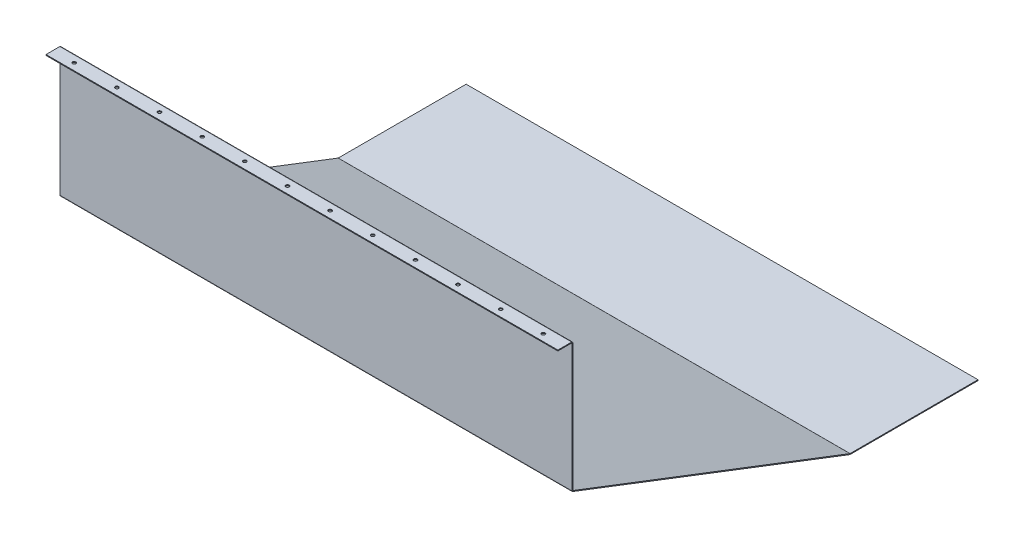
SolidWorks part; units mm, degrees
note: The reader was unsure of these and kept them because the rebuilt part matched: thickness of "Base-Flange1", "Edge-Flange1", "Sheet-Metal3", "Sheet-Metal4", "Sheet-Metal5"; bend radius of "BaseBend1", "BaseBend2"; flange length of "Edge-Flange1".
material "AISI 304"
ref_plane "Front Plane" through (0, 0, 0) normal (0, 0, 1) x (1, 0, 0)
ref_plane "Top Plane" through (0, 0, 0) normal (0, 1, 0) x (1, 0, 0)
ref_plane "Right Plane" through (0, 0, 0) normal (1, 0, 0) x (0, 0, -1)
sketch "Sketch1" plane through (0, 0, 0) normal (1, 0, 0) x (0, 0, -1)
  line L0 (0, 0) -> (0, -300)
  line L1 (0, -300) -> (650, -550)
  line L3 (950, 0) -> (0, 0) construction
  line L4 (0, -300) -> (950, -300) construction
  line L5 (950, 0) -> (950, -550) construction
  line L6 (950, -550) -> (650, -550)
  dimension "D3" = 950
  dimension "D2" = 550
  dimension "D4" = 300
  dimension "D1" = 300
base flange "Base-Flange1" sketch "Sketch1" end condition mid plane depth 1200 reverse direction no thickness 2 reverse thickness direction yes bend radius 0.7366
bend "BaseBend1" bend radius 0.7366 bend angle 21.038 parameters "D5"=1
bend "BaseBend2" bend radius 0.7366 bend angle 68.962 parameters "D5"=2
edge flange "Edge-Flange1" sketch "Sketch6" flange angle 90 flange length 35 flange position bend outside bend radius 0.7366 thickness 2 relief rectangular parameters "D6"=10
sketch "Sketch6" plane through (0, 0, 2) normal (0, -1, 0) x (1, 0, 0)
  line L2 (-600, 0) -> (-600, 33)
  line L3 (-600, 33) -> (600, 33)
  line L4 (600, 33) -> (600, 0)
  line L5 (600, 0) -> (-600, 0) construction
  line L6 (600, 0) -> (-600, 0)
bend "EdgeBend1" bend radius 0.7366 bend angle 90 parameters "D5"=3
sketch "Sketch7" plane through (0, 0.7366, 0) normal (0, -1, 0) x (1, 0, 0)
  line L0 (-600, 18.8683) -> (-550, 18.8683) construction
  line L2 (550, 18.8683) -> (600, 18.8683) construction
  line L5 (-600, 35) -> (-600, 2.7366) construction
  line L6 (600, 2.7366) -> (600, 35) construction
  circle A0 centre (-550, 18.8683) radius 4
  circle A1 centre (-450, 18.8683) radius 4
  circle A2 centre (-350, 18.8683) radius 4
  circle A3 centre (-250, 18.8683) radius 4
  circle A4 centre (-150, 18.8683) radius 4
  circle A5 centre (-50, 18.8683) radius 4
  circle A6 centre (50, 18.8683) radius 4
  circle A7 centre (150, 18.8683) radius 4
  circle A8 centre (250, 18.8683) radius 4
  circle A9 centre (350, 18.8683) radius 4
  circle A10 centre (450, 18.8683) radius 4
  circle A11 centre (550, 18.8683) radius 4
  dimension "D1" = 8
  dimension "D3" = 100
  dimension "D2" = 12
extrude "Cut-Extrude1" cut sketch "Sketch7" against normal blind 10
sketch "Bend-Lines1" [suppressed] plane through (0, 0, 0) normal (0, 1, 0) x (1, 0, 0)
sketch "Bounding-Box1" [suppressed] plane through (0, 0, 0) normal (0, 1, 0) x (1, 0, 0)
sheet metal parameters "Sheet-Metal3" thickness 2 parameters "D1"=0.7366
flat pattern "Flat-Pattern3" [suppressed]
sketch "Bend-Lines2" plane through (0, -280.2431, 80.0694) normal (0, -0.9615, 0.2747) x (-1, 0, 0)
  line L0 (600, 81.5266) -> (-600, 81.5266) construction
  line L1 (-600, 810.6354) -> (600, 810.6354) construction
  line L2 (600, 81.5266) -> (-600, 81.5266) construction
  line L3 (-600, 810.6354) -> (600, 810.6354) construction
sketch3d "Bounding-Box2" [suppressed]
  line L0 (1200, -301.7796, 0) -> (1200, 1028.4271, 0) construction
  line L1 (0, -301.7796, 0) -> (0, 1028.4271, 0) construction
  line L2 (1200, -301.7796, 0) -> (0, -301.7796, 0) construction
  line L3 (1200, 1028.4271, 0) -> (0, 1028.4271, 0) construction
bend of the flat pattern "Flatten-<BaseBend1>1"
bend of the flat pattern "Flatten-<BaseBend2>1"
sheet metal parameters "Sheet-Metal4" thickness 2 parameters "D1"=0.7366
flat pattern "Flat-Pattern3"
sketch "Bend-Lines2" plane through (0, -275.9656, 84.9125) normal (0, -0.9558, 0.2941) x (-1, 0, 0)
  line L0 (600, 87.6651) -> (-600, 87.6651) construction
  line L1 (-600, 768.4477) -> (600, 768.4477) construction
  line L2 (600, 87.6651) -> (-600, 87.6651) construction
  line L3 (-600, 768.4477) -> (600, 768.4477) construction
  line L4 (600, -214.2596) -> (-600, -214.2596) construction
  line L5 (600, -214.2596) -> (-600, -214.2596) construction
sketch3d "Bounding-Box2" [suppressed]
  line L0 (1200, -336.1126, 0) -> (1200, 980.3704, 0) construction
  line L1 (0, -336.1126, 0) -> (0, 980.3704, 0) construction
  line L2 (1200, -336.1126, 0) -> (0, -336.1126, 0) construction
  line L3 (1200, 980.3704, 0) -> (0, 980.3704, 0) construction
bend of the flat pattern "Flatten-<BaseBend1>1"
bend of the flat pattern "Flatten-<BaseBend2>1"
bend of the flat pattern "Flatten-<EdgeBend1>1"
sheet metal parameters "Sheet-Metal5" thickness 2 parameters "D1"=0.7366
flat pattern "Flat-Pattern3"
sketch "Bend-Lines2" plane through (0, -263.2069, 101.2334) normal (0, -0.9333, 0.359) x (-1, 0, 0)
  line L0 (600, 107.1545) -> (-600, 107.1545) construction
  line L1 (-600, 804.2952) -> (600, 804.2952) construction
  line L2 (600, 107.1545) -> (-600, 107.1545) construction
  line L3 (-600, 804.2952) -> (600, 804.2952) construction
  line L4 (600, -194.7486) -> (-600, -194.7486) construction
  line L5 (600, -194.7486) -> (-600, -194.7486) construction
sketch3d "Bounding-Box2" [suppressed]
  line L0 (1200, -336.0697, 0) -> (1200, 996.7835, 0) construction
  line L1 (0, -336.0697, 0) -> (0, 996.7835, 0) construction
  line L2 (1200, -336.0697, 0) -> (0, -336.0697, 0) construction
  line L3 (1200, 996.7835, 0) -> (0, 996.7835, 0) construction
bend of the flat pattern "Flatten-<BaseBend1>1"
bend of the flat pattern "Flatten-<BaseBend2>1"
bend of the flat pattern "Flatten-<EdgeBend1>1"
equation "\"splash plate length\"= 400"
equation "\"splash plate air gap\"= 200"
equation "\"splash plate slot count\"= 11"
equation "\"splash plate slot length\"= 50"
equation "\"splash plate slot height\"= 50"
equation "\"splash plate slot offset\"= 65"
equation "\"water tray depth\"= 150"
equation "\"water tray width\"= 200"
equation "\"dimple panel slot count\"= 119"
equation "\"dimple panel slot length\"= 10"
equation "\"dimple panel slot width\"= 5"
equation "\"dimple panel slot offset\"= 10"
equation "\"sump base flat section width\"= 300"
equation "\"sump depth\"= 500"
equation "\"thickness 1\" = 2"
equation "\"thickness radius 1\"= 3.7366"
equation "\"thickness 2\"= 3"
equation "\"connecting flange\"= 35"
equation "\"connecting flange holes\"= 8"
equation "\"connecting flange hole gap\"= 100"
equation "\"main length\"= 1200"
equation "\"main width\"= 1200"
equation "\"divider panel distance offset\"= 296"
equation "\"top panel slot length\"= 250"
equation "\"top panel slot width\"= 700"
equation "\"side panel length\"= 1200"
equation "\"side panel width\"= 950"
equation "\"access hatch length\" = \"access hatch cutout length\" + \"access hatch offset\" * 2"
equation "\"access hatch width\" = \"access hatch cutout width\" + \"access hatch offset\" * 2"
equation "\"access hatch offset X\"= 100"
equation "\"access hatch offset Y\"= 100"
equation "\"back panel access hatch length\"= 1150"
equation "\"back panel access hatch width\"= 206"
equation "\"back panel access hatch flange\"= 40"
equation "\"slotted panel length\" = \"main length\" + 100"
equation "\"slotted panel width\" = \"main width\""
equation "\"slot count x\"= 4"
equation "\"slot count y\"= 9"
equation "\"slot offset\" = \"water tray depth\""
equation "\"slot length\"= 30"
equation "\"slot width\"= 200"
equation "\"slot offset x\" = \"slot length\" + \"slot offset\""
equation "\"slot offset y\" = \"slot width\" + \"slot offset\""
equation "\"drift eliminator size offset\"= 5"
equation "\"drift eliminator length\"= \"back panel access hatch length\" - \"drift eliminator size offset\""
equation "\"drift eliminator width\"= \"back panel access hatch width\" - \"drift eliminator size offset\""
equation "\"drift eliminator depth\" = \"divider panel distance offset\""
equation "\"guide rail flange\"= 40"
equation "\"guid rail flange mount side\"= 20"
equation "\"guid rail back length\" = \"main width\" - \"guide rail flange\" * 2"
equation "\"splash plate width\" = \"main width\""
equation "\"water tray panel length\"= 473"
equation "\"dimpled panel length\" = \"main length\" - 200 - \"water tray depth\"/2"
equation "\"dimpled panel top offset\" = \"water tray depth\"/2"
equation "\"dimpled panel width\" = \"main width\""
equation "\"dimple panel slot count\"= 36"
equation "\"dimple panel slot length\"= 8"
equation "\"dimple panel slot width\"= 8"
equation "\"dimple panel slot offset\"= 25"
equation "\"sump upper depth\"= 300"
equation "\"sump depth\"= 550"
equation "\"leg length\" = \"sump depth\" + 150"
equation "\"leg width\"= 80"
equation "\"leg depth\"= 40"
equation "\"leg support plate size\" = \"leg width\" - \"thickness 2\" * 2"
equation "\"leg base plate thickness\"= 8"
equation "\"D3@Sketch1\"=\"side panel width\""
equation "\"D2@Sketch1\"=\"sump depth\""
equation "\"D4@Sketch1\"=\"sump base flat section width\""
equation "\"D1@Sketch1\"=\"sump upper depth\""
equation "\"D3@Sketch7\"=\"connecting flange hole gap\""
equation "\"D1@Sketch7\"=\"connecting flange holes\""
